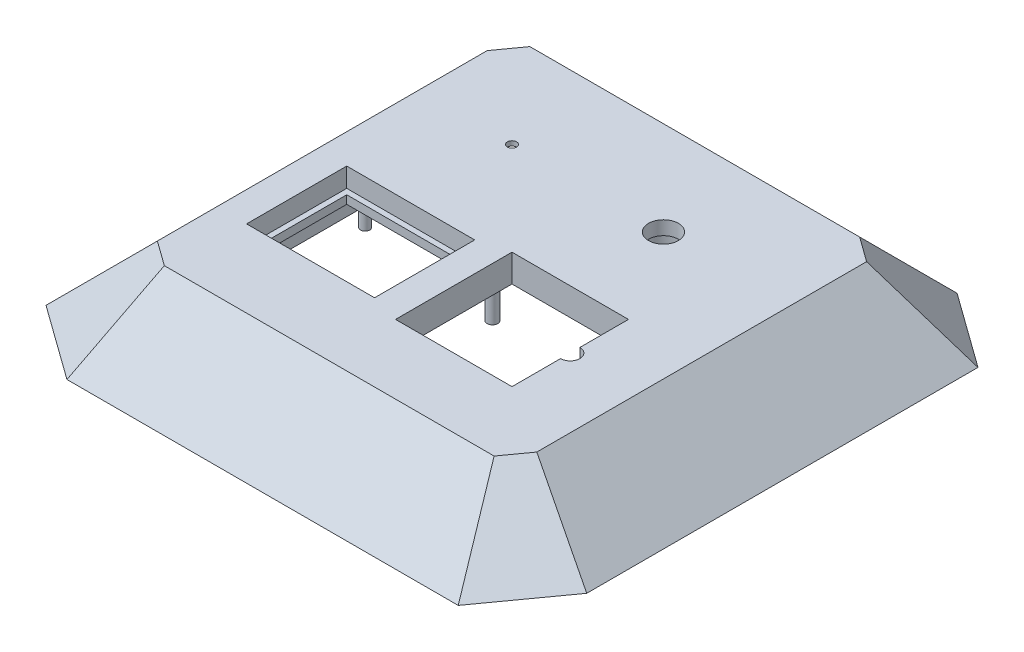
SolidWorks part; units mm, degrees
ref_plane "Front Plane" through (0, 0, 0) normal (0, 0, 1) x (1, 0, 0)
ref_plane "Top Plane" through (0, 0, 0) normal (0, 1, 0) x (1, 0, 0)
ref_plane "Right Plane" through (0, 0, 0) normal (1, 0, 0) x (0, 0, -1)
sketch "Sketch1" plane through (0, 0, 0) normal (0, 1, 0) x (1, 0, 0)
  line L0 (-47.3454, -21.7516) -> (37.6546, -21.7516)
  line L1 (37.6546, -21.7516) -> (49.3368, -5.5181)
  line L2 (49.3368, -5.5181) -> (49.3368, 79.4819)
  line L3 (49.3368, 79.4819) -> (33.1033, 91.1641)
  line L4 (33.1033, 91.1641) -> (-51.8967, 91.1641)
  line L5 (-51.8967, 91.1641) -> (-63.5789, 74.9306)
  line L6 (-63.5789, 74.9306) -> (-63.5789, -10.0694)
  line L7 (-63.5789, -10.0694) -> (-47.3454, -21.7516)
  dimension "D2" = 85
  dimension "D3" = 85
  dimension "D4" = 144.26
  dimension "D5" = 144.26
  dimension "D6" = 85
  dimension "D7" = 144.26
  dimension "D8" = 20
  dimension "D9" = 85
  dimension "D10" = 20
  dimension "D11" = 20
extrude "Boss-Extrude2" add sketch "Sketch1" along normal blind 16
sketch "Sketch4" plane through (0, 0, 0) normal (0, -1, 0) x (1, 0, 0)
  line L16 (-42.1868, 5.7516) -> (-47.5789, 1.8712)
  line L17 (-47.5789, 1.8712) -> (-47.5789, -69.772)
  line L18 (-47.5789, -69.772) -> (-43.6985, -75.1641)
  line L19 (-43.6985, -75.1641) -> (27.9447, -75.1641)
  line L20 (27.9447, -75.1641) -> (33.3368, -71.2838)
  line L21 (33.3368, -71.2838) -> (33.3368, 0.3594)
  line L22 (33.3368, 0.3594) -> (29.4564, 5.7516)
  line L23 (29.4564, 5.7516) -> (-42.1868, 5.7516)
  line L24 (-42.1868, 5.7516) -> (-47.5789, 1.8712)
  line L25 (-47.5789, 1.8712) -> (-47.5789, -69.772)
  line L26 (-47.5789, -69.772) -> (-43.6985, -75.1641)
  line L27 (-43.6985, -75.1641) -> (27.9447, -75.1641)
  line L28 (27.9447, -75.1641) -> (33.3368, -71.2838)
  line L29 (33.3368, -71.2838) -> (33.3368, 0.3594)
  line L30 (33.3368, 0.3594) -> (29.4564, 5.7516)
  line L31 (29.4564, 5.7516) -> (-42.1868, 5.7516)
  dimension "D1" = 16
chamfer "Chamfer1" distance 16 angle 45 8 edges at (-63.5789, 16, -32.4306) (-57.7378, 16, -83.0473) (-9.3967, 16, -91.1641) (41.22, 16, -85.323) (49.3368, 16, -36.9819) (43.4957, 16, 13.6348) (-4.8454, 16, 21.7516) (-55.4621, 16, 15.9105)
extrude "Cut-Extrude3" cut sketch "Sketch4" against normal blind 10
sketch "Sketch6" plane through (0, 16, 0) normal (0, 1, 0) x (1, 0, 0)
  line L0 (33.3368, -0.3594) -> (33.3368, 71.2838) construction
  line L1 (-6.9632, 34.5484) -> (18.3368, 34.5484)
  line L2 (-6.9632, 34.5484) -> (-6.9632, 9.2484)
  line L3 (-6.9632, 9.2484) -> (18.3368, 9.2484)
  line L4 (18.3368, 34.5484) -> (18.3368, 9.2484)
  line L5 (-42.1868, -5.7516) -> (29.4564, -5.7516) construction
  dimension "D1" = 25.3
  dimension "D2" = 25.3
  dimension "D3" = 15
  dimension "D4" = 15
extrude "Cut-Extrude4" cut sketch "Sketch6" against normal up to next
sketch "Sketch7" plane through (0, 10, 0) normal (0, -1, 0) x (1, 0, 0)
  line L0 (18.3368, -9.2484) -> (18.3368, -34.5484) construction
  circle A0 centre (18.3368, -21.8984) radius 2.0981
extrude "Cut-Extrude5" cut sketch "Sketch7" against normal up to next
sketch "Sketch8" plane through (0, 10, 0) normal (0, -1, 0) x (1, 0, 0)
  line L0 (-11.7632, -21.9984) -> (30.1662, -21.9984) construction
  line L1 (-11.7632, -8.8984) -> (24.2368, -8.8984)
  line L2 (-11.7632, -8.8984) -> (-11.7632, -35.0984)
  line L3 (-11.7632, -35.0984) -> (24.2368, -35.0984)
  line L4 (24.2368, -8.8984) -> (24.2368, -35.0984)
  line L5 (6.2368, -8.8984) -> (6.2368, -38.2867) construction
  line L6 (33.3368, -71.2838) -> (33.3368, 0.3594) construction
  line L7 (29.4564, 5.7516) -> (-42.1868, 5.7516) construction
  circle A0 centre (-9.2132, -11.4484) radius 1.15
  circle A1 centre (21.6868, -11.4484) radius 1.15
  circle A2 centre (21.6868, -32.5484) radius 1.15
  circle A3 centre (-9.2132, -32.5484) radius 1.15
  dimension "D3" = 2.3
  dimension "D4" = 2.55
  dimension "D5" = 2.55
  dimension "D6" = 9.1
  dimension "D1" = 36
  dimension "D2" = 26.2
  dimension "D7" = 14.65
extrude "Boss-Extrude3" add sketch "Sketch8" along normal blind 7 contours A0 | A1 | A2 | A3 region at (-9.2132, 10, -11.4484) region at (21.6868, 10, -11.4484) region at (21.6868, 10, -32.5484)
sketch "Sketch9" plane through (0, 10, 0) normal (0, -1, 0) x (1, 0, 0)
  line L2 (-47.5789, 1.8712) -> (-47.5789, -69.772) construction
  line L3 (-43.6985, -75.1641) -> (27.9447, -75.1641) construction
  circle A0 centre (-27.2189, -54.8041) radius 15.65
  dimension "D1" = 20.36
  dimension "D2" = 20.36
  dimension "D3" = 31.3
extrude "Cut-Extrude6" cut sketch "Sketch9" against normal blind 5
sketch "Sketch10" plane through (0, 15, 0) normal (0, -1, 0) x (1, 0, 0)
  circle A0 centre (-27.2189, -54.8041) radius 1
  dimension "D1" = 2
extrude "Cut-Extrude7" cut sketch "Sketch10" against normal up to next
sketch "Sketch11" plane through (0, 16, 0) normal (0, 1, 0) x (1, 0, 0)
  line L0 (-14.7144, 21.8984) -> (-6.9632, 21.8984) construction
  line L1 (-14.7144, 35.3984) -> (-39.7144, 35.3984)
  line L2 (-14.7144, 35.3984) -> (-14.7144, 8.3984)
  line L3 (-14.7144, 8.3984) -> (-39.7144, 8.3984)
  line L4 (-39.7144, 35.3984) -> (-39.7144, 8.3984)
  line L5 (-6.9632, 34.5484) -> (-6.9632, 9.2484) construction
  line L6 (-27.2144, 35.3984) -> (-27.2144, 2.0931) construction
  line L7 (-14.7144, 21.8984) -> (-44.3409, 21.8984) construction
  circle A0 centre (-37.5644, 33.2484) radius 1
  circle A1 centre (-16.8644, 33.2484) radius 1
  circle A2 centre (-16.8644, 10.5484) radius 1
  circle A3 centre (-37.5644, 10.5484) radius 1
  dimension "D3" = 2
  dimension "D4" = 2.15
  dimension "D5" = 2.15
  dimension "D1" = 25
  dimension "D2" = 27
extrude "Boss-Extrude4" add sketch "Sketch11" against normal blind 10 contours A0 | A1 | A2 | A3
sketch "Sketch12" plane through (0, 16, 0) normal (0, 1, 0) x (1, 0, 0)
  line L0 (-14.7144, 35.3984) -> (-14.7144, 8.3984) construction
  line L1 (-39.9144, 31.5984) -> (-14.5144, 31.5984)
  line L2 (-39.9144, 31.5984) -> (-39.9144, 12.2384)
  line L3 (-39.9144, 12.2384) -> (-14.5144, 12.2384)
  line L4 (-14.5144, 31.5984) -> (-14.5144, 12.2384)
  line L5 (-39.7144, 35.3984) -> (-39.7144, 8.3984) construction
  line L6 (-14.7144, 35.3984) -> (-39.7144, 35.3984) construction
  line L7 (-14.7144, 8.3984) -> (-39.7144, 8.3984) construction
  dimension "D1" = 0.2
  dimension "D2" = 0.2
  dimension "D3" = 3.8
  dimension "D4" = 3.84
extrude "Cut-Extrude8" cut sketch "Sketch12" against normal through all
sketch "Sketch13" plane through (0, 16, 0) normal (0, 1, 0) x (1, 0, 0)
  line L0 (-14.5144, 31.5984) -> (-39.9144, 31.5984) construction
  line L1 (-41.1144, 32.7984) -> (-13.3144, 32.7984)
  line L2 (-41.1144, 32.7984) -> (-41.1144, 11.0384)
  line L3 (-41.1144, 11.0384) -> (-13.3144, 11.0384)
  line L4 (-13.3144, 32.7984) -> (-13.3144, 11.0384)
  line L5 (-39.9144, 31.5984) -> (-39.9144, 12.2384) construction
  line L6 (-14.5144, 12.2384) -> (-14.5144, 31.5984) construction
  line L7 (-39.9144, 12.2384) -> (-14.5144, 12.2384) construction
  dimension "D1" = 1.2
  dimension "D2" = 1.2
  dimension "D3" = 1.2
  dimension "D4" = 1.2
extrude "Cut-Extrude9" cut sketch "Sketch13" against normal blind 4.2
sketch "Sketch14" plane through (0, 16, 0) normal (0, 1, 0) x (1, 0, 0)
  line L0 (5.6868, 54.8041) -> (-27.2189, 54.8041) construction
  line L1 (5.6868, 54.8041) -> (5.6868, 34.5484) construction
  line L2 (18.3368, 34.5484) -> (-6.9632, 34.5484) construction
  circle A0 centre (5.6868, 54.8041) radius 3.25
  dimension "D1" = 6.5
extrude "Cut-Extrude10" cut sketch "Sketch14" against normal through all
sketch "Sketch15" plane through (0, 10, 0) normal (0, -1, 0) x (1, 0, 0)
  circle A0 centre (5.6868, -54.8041) radius 4.25
  dimension "D1" = 8.5
extrude "Cut-Extrude11" cut sketch "Sketch15" against normal blind 3
